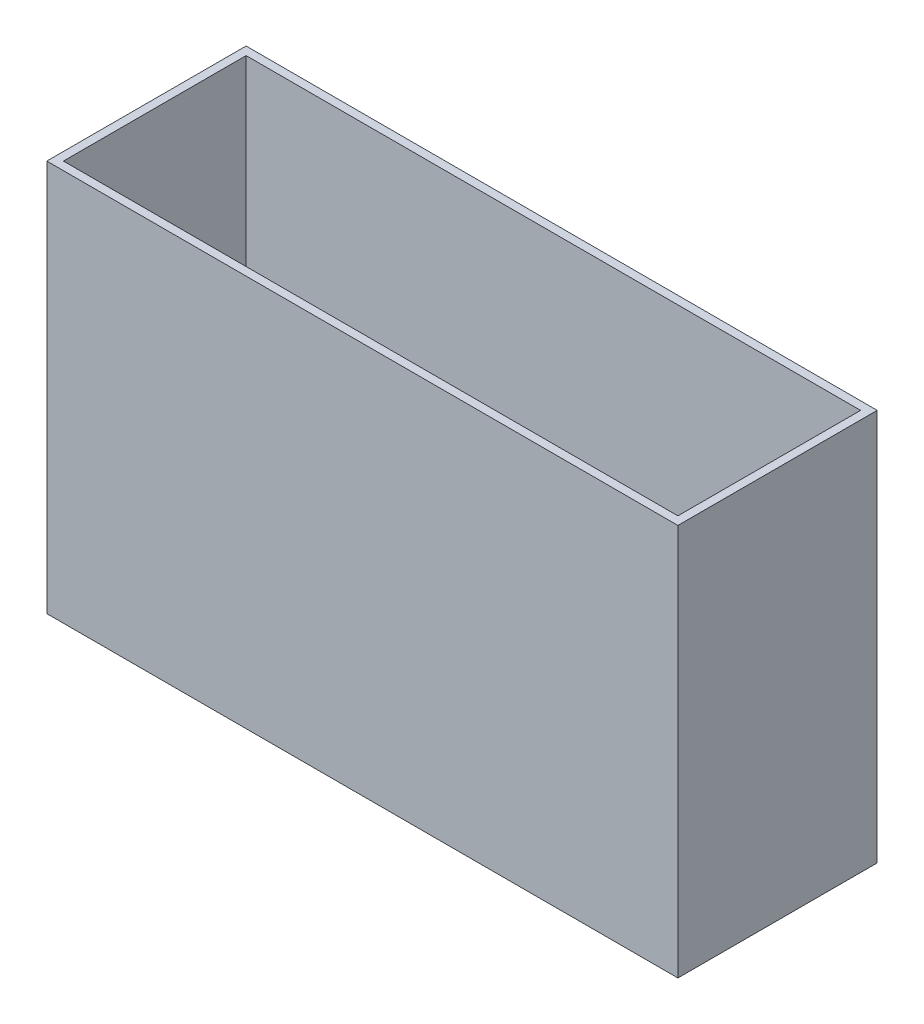
SolidWorks part; units mm, degrees
ref_plane "Front" through (0, 0, 0) normal (0, 0, 1) x (1, 0, 0)
ref_plane "Top" through (0, 0, 0) normal (0, 1, 0) x (1, 0, 0)
ref_plane "Right" through (0, 0, 0) normal (1, 0, 0) x (0, 0, -1)
sketch "Sketch1" plane through (0, 0, 0) normal (0, 1, 0) x (1, 0, 0)
  line L1 (-120.65, 38.1) -> (120.65, 38.1)
  line L2 (-120.65, 38.1) -> (-120.65, -38.1)
  line L3 (-120.65, -38.1) -> (120.65, -38.1)
  line L4 (120.65, 38.1) -> (120.65, -38.1)
  line L5 (-120.65, 38.1) -> (120.65, -38.1) construction
  line L6 (-120.65, -38.1) -> (120.65, 38.1) construction
  line L7 (-102.87, 2.794) -> (102.87, 2.794)
  line L8 (-102.87, 2.794) -> (-102.87, -2.794)
  line L9 (-102.87, -2.794) -> (102.87, -2.794)
  line L10 (102.87, 2.794) -> (102.87, -2.794)
  line L11 (-102.87, 2.794) -> (102.87, -2.794) construction
  line L12 (-102.87, -2.794) -> (102.87, 2.794) construction
  point P0 (0, 0)
  point P6 (0, 0)
  point P7 (0, 0)
  dimension "D1" = 241.3
  dimension "D2" = 76.2
  dimension "D3" = 5.588
  dimension "D4" = 205.74
extrude "Boss-Extrude1" add sketch "Sketch1" along normal blind 149.86
shell "Shell1" thickness 3.175 removed face at (0, 0, 0) removed face at (0, 74.93, -2.794) removed face at (0, 74.93, 2.794) removed face at (-102.87, 74.93, 0) removed face at (102.87, 74.93, 0) removed face at (0, 149.86, 0)
sketch "Sketch3" plane through (0, 0, 38.1) normal (0, 0, 1) x (1, 0, 0)
  line L3 (107.95, 52.9447) -> (66.675, 28.7862)
  line L8 (66.675, 28.7862) -> (107.95, 14.8447)
  line L9 (98.425, 12.7) -> (60.325, 25.5691)
  line L10 (97.5972, 52.7713) -> (60.325, 30.9557)
  line L11 (60.325, 12.7) -> (60.325, 44.8724) construction
  line L12 (12.7, 28.7862) -> (107.95, 28.7862) construction
  line L13 (22.225, 12.7) -> (60.325, 25.5691)
  line L14 (53.975, 28.7862) -> (12.7, 14.8447)
  line L15 (12.7, 52.9447) -> (53.975, 28.7862)
  line L16 (23.0528, 52.7713) -> (60.325, 30.9557)
  line L20 (0, -41.91) -> (0, 41.91) construction
  line L21 (-107.95, 52.9447) -> (-66.675, 28.7862)
  line L22 (-66.675, 28.7862) -> (-107.95, 14.8447)
  line L23 (-107.95, 52.9447) -> (-107.95, 14.8447)
  line L24 (-22.225, 12.7) -> (-60.325, 25.5691)
  line L25 (-98.425, 12.7) -> (-60.325, 25.5691)
  line L26 (-22.225, 12.7) -> (-98.425, 12.7)
  line L27 (-12.7, 52.9447) -> (-53.975, 28.7862)
  line L28 (-53.975, 28.7862) -> (-12.7, 14.8447)
  line L33 (-12.7, 52.9447) -> (-12.7, 14.8447)
  line L34 (107.95, 52.9447) -> (107.95, 14.8447)
  line L35 (97.5972, 52.7713) -> (23.0528, 52.7713)
  line L36 (12.7, 52.9447) -> (12.7, 14.8447)
  line L37 (22.225, 12.7) -> (98.425, 12.7)
  line L38 (-97.5972, 52.7713) -> (-60.325, 30.9557)
  line L39 (-23.0528, 52.7713) -> (-60.325, 30.9557)
  line L40 (-97.5972, 52.7713) -> (-23.0528, 52.7713)
  dimension "D1" = 38.1
  dimension "D2" = 38.1
  dimension "D3" = 5.08
  dimension "D4" = 5.08
  dimension "D5" = 12.7
  dimension "D6" = 38.1
extrude "Cut-Extrude1" cut sketch "Sketch3" against normal up to next from surface starting at face at (0, 74.93, -34.925)
equation "\"0.1025n\"=0.1"
